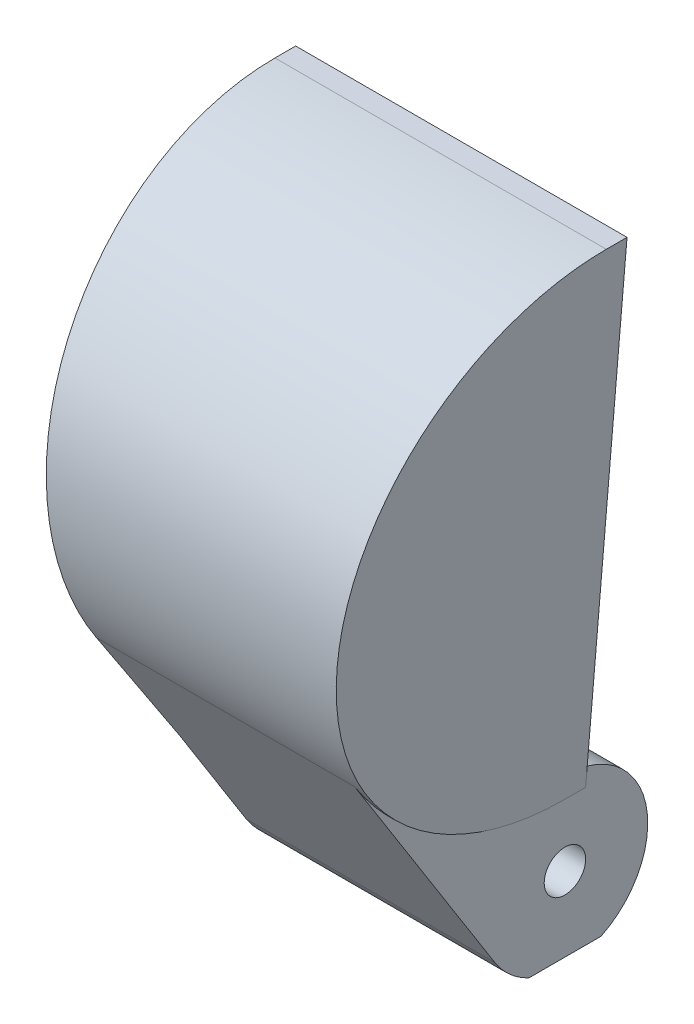
SolidWorks part; units mm, degrees
material "6061-T6 (SS)"
ref_plane "Front Plane" through (0, 0, 0) normal (0, 0, 1) x (1, 0, 0)
ref_plane "Top Plane" through (0, 0, 0) normal (0, 1, 0) x (1, 0, 0)
ref_plane "Right Plane" through (0, 0, 0) normal (1, 0, 0) x (0, 0, -1)
sketch "ExcavatorReferenceSize" plane through (0, 0, 0) normal (0, 1, 0) x (1, 0, 0)
  line L1 (-25.4, -12.7) -> (25.4, -12.7)
  line L2 (-25.4, -12.7) -> (-25.4, 12.7)
  line L3 (-25.4, 12.7) -> (25.4, 12.7)
  line L4 (25.4, -12.7) -> (25.4, 12.7)
  line L5 (-25.4, -12.7) -> (25.4, 12.7) construction
  line L6 (-25.4, 12.7) -> (25.4, -12.7) construction
  point P0 (0, 0)
  dimension "D1" = 25.4
  dimension "D2" = 50.8
sketch "Sketch2" plane through (0, 0, 0) normal (1, 0, 0) x (0, 0, -1)
  line L0 (0, 0) -> (0, 76.2)
  line L1 (0, 0) -> (8.9803, -8.9803) construction
  line L2 (0, 0) -> (0, 97.7406) construction
  arc A0 (0, 76.2) -> (0, 0) centre (0, 38.1) ccw
  dimension "D1" = 76.2
  dimension "D2" = 12.7
  dimension "D3" = 135
extrude "Boss-Extrude1" add sketch "Sketch2" along normal mid plane 50.8
sketch "Sketch15" plane through (0, 0, 0) normal (0, 0, -1) x (-1, 0, 0)
  line L1 (-25.4, 0) -> (-25.4, 76.2)
  line L2 (0, 0) -> (0, 31.962) construction
  line L3 (25.4, 0) -> (19.05, 0)
  line L4 (25.4, 0) -> (25.4, 76.2)
  line L9 (19.05, 0) -> (25.4, 76.2)
  line L10 (-19.05, 0) -> (-25.4, 76.2)
  line L11 (-25.4, 0) -> (-19.05, 0)
  dimension "D1" = 6.35
extrude "Cut-Extrude9" cut sketch "Sketch15" against normal through all
shell "Shell1" thickness 3.175 removed face at (0, 38.1, 0)
sketch "Sketch4" plane through (0, 0, 0) normal (1, 0, 0) x (0, 0, -1)
  line L0 (0, 0) -> (0, -44.7111) construction
  line L1 (0, 0) -> (0, 113.2937) construction
  circle A1 centre (0, -9.525) radius 12.7
  arc A2 (0, 73.025) -> (0, 3.175) centre (0, 38.1) ccw
  arc A3 (0, 73.025) -> (0, 3.175) centre (0, 38.1) ccw construction
  point P9 (0, 3.175)
  dimension "D1" = 25.4
  dimension "D2" = 180
  dimension "D3" = 12.7
extrude "Boss-Extrude3" add sketch "Sketch4" along normal mid plane 38.1
sketch "Sketch5" plane through (0, 0, 0) normal (0, 0, -1) x (-1, 0, 0)
  line L3 (19.05, 3.175) -> (19.05, 0)
  line L11 (-19.05, 0) -> (-19.05, 3.175)
  line L12 (-25.4, 76.2) -> (25.4, 76.2) construction
  line L15 (-25.4, 76.2) -> (25.4, 76.2)
  line L21 (-19.05, 3.175) -> (-16.1286, 3.175)
  line L22 (-19.05, 3.175) -> (-16.1286, 3.175)
  line L23 (-21.9494, 73.025) -> (21.9494, 73.025)
  line L24 (16.1286, 3.175) -> (19.05, 3.175)
  line L25 (16.1286, 3.175) -> (19.05, 3.175)
  line L27 (19.05, 0) -> (25.4, 76.2)
  line L28 (25.4, 76.2) -> (-25.4, 76.2)
  line L29 (19.05, 3.175) -> (19.05, 0)
  line L33 (-21.9494, 73.025) -> (21.9494, 73.025)
  line L43 (19.05, 0) -> (25.4, 76.2)
  line L44 (-19.05, 0) -> (-19.05, 3.175)
  line L45 (21.9494, 73.025) -> (16.1286, 3.175)
  line L46 (21.9494, 73.025) -> (16.1286, 3.175)
  line L47 (-16.1286, 3.175) -> (-21.9494, 73.025)
  line L48 (-16.1286, 3.175) -> (-21.9494, 73.025)
  line L49 (-25.4, 76.2) -> (-19.05, 0)
  line L50 (-25.4, 76.2) -> (-19.05, 0)
  dimension "D2" = 0
sketch "Sketch7" plane through (-19.05, 0, 0) normal (-1, 0, 0) x (0, 0, 1)
  circle A2 centre (0, -9.525) radius 12.7 construction
  circle A3 centre (0, -9.525) radius 3.175
  circle A4 centre (0, -9.525) radius 12.7 construction
  dimension "D1" = 6.35
extrude "Cut-Extrude4" cut sketch "Sketch7" against normal up to surface (38.1 mm away) up to face at (19.05, -6.6093, -0.0583)
sketch "Sketch8" plane through (19.05, 0, 0) normal (1, 0, 0) x (0, 0, -1)
  line L3 (-32.229, 17.78) -> (-10.743, -16.2983)
  line L10 (0, 0) -> (4.7601, 0) construction
  line L11 (-25.2112, 13.9308) -> (-32.229, 17.78)
  arc A0 (-7.4768, 0.7408) -> (-7.4768, 0.7408) centre (0, 38.1) ccw
  arc A2 (0, 76.2) -> (-7.4768, 0.7408) centre (0, 38.1) ccw
  circle A3 centre (0, -9.525) radius 12.7 construction
  arc A5 (0, 76.2) -> (-32.229, 17.78) centre (0, 38.1) ccw construction
  arc A6 (0, 73.025) -> (0, 3.175) centre (0, 38.1) ccw construction
  arc A7 (0, 3.175) -> (-10.743, -16.2983) centre (0, -9.525) ccw
  arc A9 (0, 73.025) -> (-34.9248, 38.2321) centre (0, 38.1) ccw
  arc A10 (-25.2112, 13.9308) -> (0, 3.175) centre (0, 38.1) ccw
  arc A11 (0, 73.025) -> (0, 3.175) centre (0, 38.1) ccw construction
  point P10 (1.1247, 0)
  point P12 (-10.743, -16.2983)
  point P18 (-25.2112, 13.9308)
  dimension "D1" = 8.0041
extrude "Boss-Extrude5" add sketch "Sketch8" against normal up to surface (38.1 mm away) up to face at (-19.05, -9.525, 3.175)
ref_plane "Plane1" through (0, -22.225, 0) normal (0, -1, 0) x (-1, 0, 0)
fillet "Fillet2" radius 12.7 2 edges at (19.039, 38.1, 34.925) (-19.039, 38.1, 34.925)
sketch "Sketch13" plane through (0, -22.225, 0) normal (0, -1, 0) x (-1, 0, 0)
  line L12 (19.05, 7.9375) -> (-19.05, 7.9375)
  line L13 (19.05, 7.9375) -> (19.05, -7.9375)
  line L14 (19.05, -7.9375) -> (-19.05, -7.9375)
  line L15 (-19.05, 7.9375) -> (-19.05, -7.9375)
  point P1 (-19.05, 0)
  point P3 (0, 0)
  point P4 (0, 7.9375)
  dimension "D1" = 38.1
  dimension "D2" = 15.875
extrude "Cut-Extrude7" cut sketch "Sketch13" against normal blind 1.27
sketch "Sketch22" plane through (18.9186, -1.5766, 0) normal (0.9965, -0.083, 0) x (0, 0, -1)
  ellipse E1 centre (0, 39.8141) end of major axis (0, 1.582) minor radius 38.1 (0, 78.0461) -> (0, 1.582) ccw construction
  ellipse E2 centre (0, 39.8141) end of major axis (0, 1.582) minor radius 38.1 (0, 78.0461) -> (0, 1.582) ccw
sketch "Sketch30" plane through (19.05, 1.582, 0) normal (-1, 0, 0) x (0, 0, -1)
  line L3 (-10.743, 17.8803) -> (-32.229, -16.198)
  line L5 (-10.743, 17.8803) -> (-32.229, -16.198)
  line L6 (0, 1.582) -> (0, -1.593)
  line L7 (0, 1.582) -> (0, -1.593)
  line L11 (5.5358, 22.537) -> (-5.5358, 22.537)
  line L15 (0, 1.582) -> (0, -1.593)
  line L21 (-10.743, 17.8803) -> (-32.229, -16.198)
  line L23 (0, 1.582) -> (0, -1.593)
  line L25 (-10.743, 17.8803) -> (-32.229, -16.198)
  line L26 (5.5358, 22.537) -> (-5.5358, 22.537)
  line L28 (5.5358, 22.537) -> (-5.5358, 22.537)
  line L29 (5.5358, 22.537) -> (-5.5358, 22.537)
  arc A2 (-5.5358, 22.537) -> (-10.743, 17.8803) centre (0, 11.107) ccw
  arc A3 (-5.5358, 22.537) -> (-10.743, 17.8803) centre (0, 11.107) ccw
  arc A4 (0, -1.593) -> (5.5358, 22.537) centre (0, 11.107) ccw
  arc A5 (0, -1.593) -> (5.5358, 22.537) centre (0, 11.107) ccw
  arc A6 (-5.5358, 22.537) -> (-10.743, 17.8803) centre (0, 11.107) ccw
  arc A7 (-5.5358, 22.537) -> (-10.743, 17.8803) centre (0, 11.107) ccw
  arc A8 (0, -1.593) -> (5.5358, 22.537) centre (0, 11.107) ccw
  arc A9 (0, -1.593) -> (5.5358, 22.537) centre (0, 11.107) ccw
  arc A11 (0, 1.582) -> (-32.229, -16.198) centre (0, -36.518) ccw
  arc A12 (0, 1.582) -> (-32.229, -16.198) centre (0, -36.518) ccw
  arc A13 (0, 1.582) -> (-32.229, -16.198) centre (0, -36.518) ccw
  arc A14 (0, 1.582) -> (-32.229, -16.198) centre (0, -36.518) ccw
  dimension "D1" = 0
  dimension "D2" = 0
sketch "Sketch31" plane through (-19.05, 0, 0) normal (-1, 0, 0) x (0, 0, 1)
  line L0 (10.743, -16.2983) -> (32.229, 17.78) construction
  line L1 (21.0189, 0) -> (32.229, 17.78)
  line L2 (0, 0) -> (21.0189, 0)
  arc A2 (0, 0) -> (32.229, 17.78) centre (0, 38.1) ccw construction
  arc A3 (0, 0) -> (32.229, 17.78) centre (0, 38.1) ccw
extrude "Boss-Extrude11" add sketch "Sketch31" along normal up to surface up to face at (-22.225, 38.1, 19.05)
ref_plane "Plane4" through (26.9875, 0, 0) normal (1, 0, 0) x (0, 0, -1)
sketch "Sketch35" plane through (0, 0, 0) normal (0, 0, -1) x (-1, 0, 0)
  line L19 (-17.468, 0.1318) -> (-23.6747, 74.6125)
  line L20 (-23.6747, 74.6125) -> (23.6747, 74.6125)
  line L21 (23.6747, 74.6125) -> (17.468, 0.1318)
  line L22 (-17.468, 0.1318) -> (-22.3852, 59.1385)
  line L24 (22.3852, 59.1385) -> (17.468, 0.1318)
  line L27 (8.1471, 74.6125) -> (-8.1471, 74.6125)
  line L28 (8.1471, 74.6125) -> (-8.1471, 74.6125)
  arc A12 (-8.1471, 74.6125) -> (-22.3852, 59.1385) centre (-8.1471, 60.325) ccw
  arc A13 (22.3852, 59.1385) -> (8.1471, 74.6125) centre (8.1471, 60.325) ccw
  arc A14 (-8.1471, 74.6125) -> (-22.3852, 59.1385) centre (-8.1471, 60.325) ccw
  arc A15 (22.3852, 59.1385) -> (8.1471, 74.6125) centre (8.1471, 60.325) ccw
  dimension "D1" = 1.5875
  dimension "D2" = 1.5875
sketch "Sketch36" plane through (0, 0, 0) normal (1, 0, 0) x (0, 0, -1)
  line L0 (0, 76.2) -> (3.175, 76.2)
  line L1 (0, 76.2) -> (0, 73.025)
  line L2 (0, 0) -> (0, 76.2) construction
  arc A0 (3.175, 76.2) -> (0, 73.025) centre (3.175, 73.025) ccw
  dimension "D1" = 3.175
  dimension "D2" = 3.175
sweep "Sweep1" add profiles "Sketch36" path "Sketch35"
ref_plane "Plane5" through (0, 0, -6.35) normal (0, 0, -1) x (-1, 0, 0)
sketch "Sketch37" plane through (0, 0, -6.35) normal (0, 0, -1) x (-1, 0, 0)
  line L2 (25.4, 76.2) -> (8.1471, 76.2)
  line L3 (23.9672, 59.0067) -> (25.4, 76.2)
  line L4 (25.4, 76.2) -> (8.1471, 76.2) construction
  line L5 (23.9672, 59.0067) -> (25.4, 76.2) construction
  arc A1 (23.9672, 59.0067) -> (8.1471, 76.2) centre (8.1471, 60.325) ccw
  arc A2 (23.9672, 59.0067) -> (8.1471, 76.2) centre (8.1471, 60.325) ccw construction
  point P5 (25.4, 76.2)
  dimension "D1" = 0
sketch "Sketch38" plane through (0, 0, 0) normal (0, 0, -1) x (-1, 0, 0)
  line L2 (25.4, 76.2) -> (8.1471, 76.2)
  line L3 (23.9672, 59.0067) -> (25.4, 76.2)
  line L4 (25.4, 76.2) -> (8.1471, 76.2)
  line L5 (23.9672, 59.0067) -> (25.4, 76.2)
  line L6 (-25.4, 76.2) -> (-23.9672, 59.0067)
  line L7 (-8.1471, 76.2) -> (-25.4, 76.2)
  line L8 (-25.4, 76.2) -> (-23.9672, 59.0067)
  line L9 (-8.1471, 76.2) -> (-25.4, 76.2)
  arc A1 (23.9672, 59.0067) -> (8.1471, 76.2) centre (8.1471, 60.325) ccw
  arc A2 (23.9672, 59.0067) -> (8.1471, 76.2) centre (8.1471, 60.325) ccw
  arc A3 (-8.1471, 76.2) -> (-23.9672, 59.0067) centre (-8.1471, 60.325) ccw
  arc A4 (-8.1471, 76.2) -> (-23.9672, 59.0067) centre (-8.1471, 60.325) ccw
  dimension "D1" = 0
  dimension "D2" = 0
extrude "Boss-Extrude16" add sketch "Sketch38" along normal blind 3.175
sketch "Sketch39" plane through (0, 0, -3.175) normal (0, 0, -1) x (-1, 0, 0)
  line L2 (14.0906, 45.6046) -> (8.9073, 62.485)
  line L3 (8.9073, 62.485) -> (-7.5591, 62.6341)
  line L6 (25.4, 76.2) -> (8.1471, 76.2) construction
  arc A1 (23.9672, 59.0067) -> (8.1471, 76.2) centre (8.1471, 60.325) ccw construction
  arc A3 (-7.5591, 62.6341) -> (14.0906, 45.6046) centre (-1.9508, 47.4876) cw
  dimension "D3" = 16.1515
  dimension "D1" = 16.8804
  dimension "D2" = 16.4664
  dimension "D4" = 0.519
